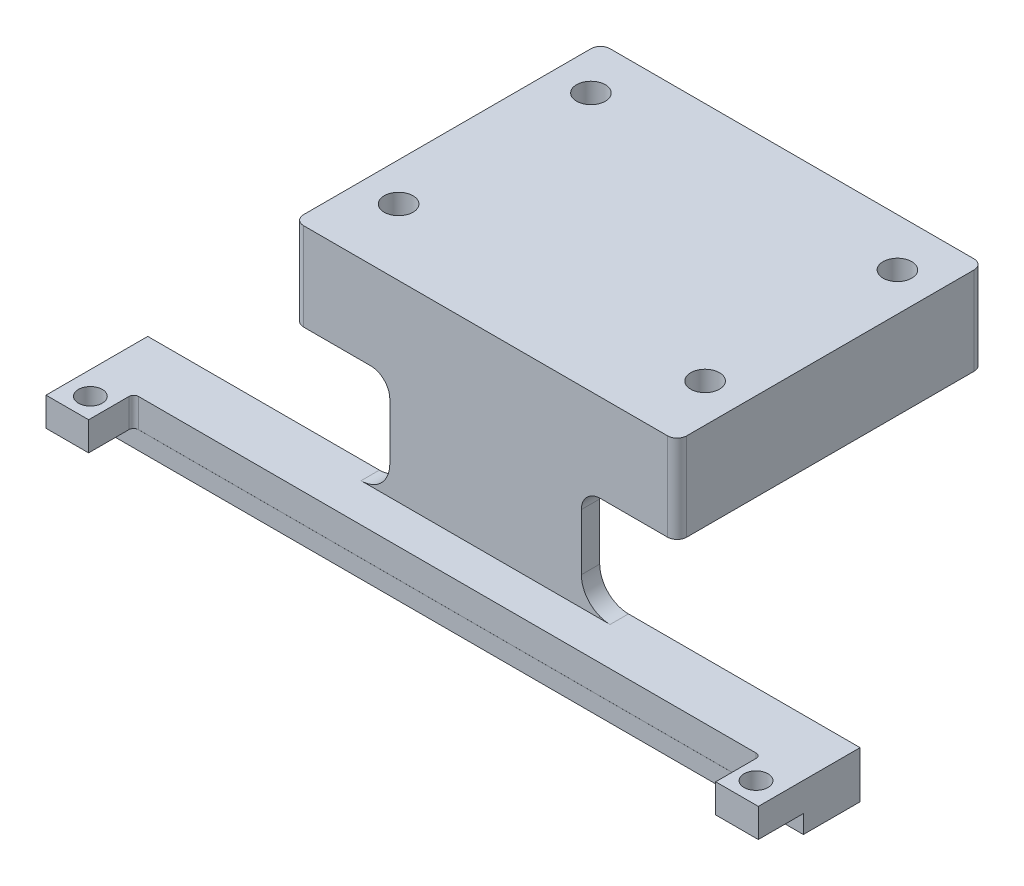
SolidWorks part; units mm, degrees
ref_plane "Ön Düzlem" through (0, 0, 0) normal (0, 0, 1) x (1, 0, 0)
ref_plane "Üst Düzlem" through (0, 0, 0) normal (0, 1, 0) x (1, 0, 0)
ref_plane "Sağ Düzlem" through (0, 0, 0) normal (1, 0, 0) x (0, 0, -1)
sketch "Çizim2" plane through (0, 0, 0) normal (0, 1, 0) x (1, 0, 0)
  line L1 (20, -16) -> (-20, -16)
  line L2 (20, -16) -> (20, 16)
  line L3 (20, 16) -> (-20, 16)
  line L4 (-20, -16) -> (-20, 16)
  line L5 (20, -16) -> (-20, 16) construction
  line L6 (20, 16) -> (-20, -16) construction
  point P0 (0, 0)
  dimension "D1" = 32
  dimension "D2" = 40
extrude "Yükseklik-Ekstrüzyon1" add sketch "Çizim2" along normal blind 9.17
sketch "Çizim3" plane through (0, 0, 0) normal (0, -1, 0) x (-1, 0, 0)
  line L0 (-20, -16) -> (-20, 16) construction
  line L1 (20, -16) -> (-20, -16)
  line L2 (20, -16) -> (20, -14.0848)
  line L3 (20, -14.0848) -> (-20, -14.0848)
  line L4 (-20, -16) -> (-20, -14.0848)
extrude "Yükseklik-Ekstrüzyon2" add sketch "Çizim3" along normal blind 12.39
sketch "Çizim4" plane through (0, 0, 16) normal (0, 0, 1) x (1, 0, 0)
  line L1 (-20, -12.39) -> (-10, -12.39)
  line L2 (-20, -12.39) -> (-20, 0)
  line L3 (-20, 0) -> (-10, 0)
  line L4 (-10, -12.39) -> (-10, 0)
  line L5 (20, -12.39) -> (10, -12.39)
  line L6 (20, -12.39) -> (20, 0)
  line L7 (20, 0) -> (10, 0)
  line L8 (10, -12.39) -> (10, 0)
  dimension "D1" = 12.39
  dimension "D2" = 12.39
  dimension "D3" = 20
  dimension "D4" = 10
extrude "Kes-Ekstrüzyon1" cut sketch "Çizim4" against normal blind 12.39
sketch "Çizim5" plane through (0, 0, 16) normal (0, 0, 1) x (1, 0, 0)
  line L0 (10, -12.39) -> (-10, -12.39) construction
  line L1 (37.185, -10.89) -> (-37.185, -10.89)
  line L2 (37.185, -10.89) -> (37.185, -13.89)
  line L3 (37.185, -13.89) -> (-37.185, -13.89)
  line L4 (-37.185, -10.89) -> (-37.185, -13.89)
  line L5 (37.185, -10.89) -> (-37.185, -13.89) construction
  line L6 (37.185, -13.89) -> (-37.185, -10.89) construction
  point P0 (0, -12.39)
  dimension "D1" = 74.37
  dimension "D2" = 3
extrude "Yükseklik-Ekstrüzyon3" add sketch "Çizim5" along normal blind 4 and the other way up to vertex (1.9152 mm away) other way up to point (-10, -12.39, 14.0848)
sketch "Çizim6" plane through (0, 0, 20) normal (0, 0, 1) x (1, 0, 0)
  line L0 (-37.185, -13.89) -> (37.185, -13.89) construction
  line L1 (-37.185, -10.89) -> (-32.735, -10.89)
  line L2 (-37.185, -10.89) -> (-37.185, -13.89)
  line L3 (-37.185, -13.89) -> (-32.735, -13.89)
  line L4 (-32.735, -10.89) -> (-32.735, -13.89)
  line L6 (37.185, -10.89) -> (32.735, -10.89)
  line L7 (37.185, -10.89) -> (37.185, -13.89)
  line L8 (37.185, -13.89) -> (32.735, -13.89)
  line L9 (32.735, -10.89) -> (32.735, -13.89)
  dimension "D1" = 4.45
  dimension "D2" = 4.45
extrude "Yükseklik-Ekstrüzyon4" add sketch "Çizim6" along normal blind 4.71
sketch "Çizim7" plane through (37.185, 0, 0) normal (1, 0, 0) x (0, 0, -1)
  line L1 (-14.0848, -13.89) -> (-20.0048, -13.89)
  line L2 (-14.0848, -13.89) -> (-14.0848, -15.79)
  line L3 (-14.0848, -15.79) -> (-20.0048, -15.79)
  line L4 (-20.0048, -13.89) -> (-20.0048, -15.79)
  dimension "D1" = 5.92
  dimension "D2" = 1.9
extrude "Yükseklik-Ekstrüzyon5" add sketch "Çizim7" against normal up to vertex (74.37 mm away) up to point (-37.185, -13.89, 14.0848)
fillet "Radyus1" radius 3 2 edges at (10, -10.89, 15.0424) (-10, -10.89, 15.0424)
fillet "Radyus2" radius 2 2 edges at (10, 0, 15.0424) (-10, 0, 15.0424)
fillet "Radyus3" radius 1 4 edges at (-20, 4.585, 16) (-20, 4.585, -16) (20, 4.585, -16) (20, 4.585, 16)
fillet "Radyus4" radius 0.5 2 edges at (-32.735, -12.39, 20) (32.735, -12.39, 20)
sketch "Çizim8" plane through (0, -10.89, 0) normal (0, 1, 0) x (1, 0, 0)
  line L0 (-37.185, -14.0848) -> (-37.185, -24.71) construction
  line L2 (-32.735, -24.71) -> (-37.185, -24.71) construction
  circle A0 centre (-34.765, -22.5) radius 1.25
  circle A1 centre (34.735, -22.5) radius 1.25
  dimension "D1" = 69.5
  dimension "D3" = 2.5
  dimension "D4" = 2.5
  dimension "D2" = 2.42
  dimension "D5" = 2.21
extrude "Kes-Ekstrüzyon2" cut sketch "Çizim8" against normal blind 10
sketch "Çizim9" plane through (0, 9.17, 0) normal (0, 1, 0) x (1, 0, 0)
  line L0 (-20, 15) -> (-20, -15) construction
  line L1 (20, -15) -> (20, 15) construction
  line L2 (19, 16) -> (-19, 16) construction
  circle A0 centre (-16, -9.08) radius 1.5
  circle A1 centre (-16, 11) radius 1.5
  circle A2 centre (16, 11) radius 1.5
  circle A3 centre (16, -9.08) radius 1.5
  point P14 (0, 0)
  point P15 (0, 0)
  dimension "D1" = 3
  dimension "D2" = 3
  dimension "D3" = 3
  dimension "D4" = 3
  dimension "D5" = 4
  dimension "D6" = 4
  dimension "D7" = 4
  dimension "D8" = 4
  dimension "D9" = 5
  dimension "D10" = 5
  dimension "D11" = 20.08
  dimension "D12" = 20.08
extrude "Kes-Ekstrüzyon3" cut sketch "Çizim9" against normal blind 10
